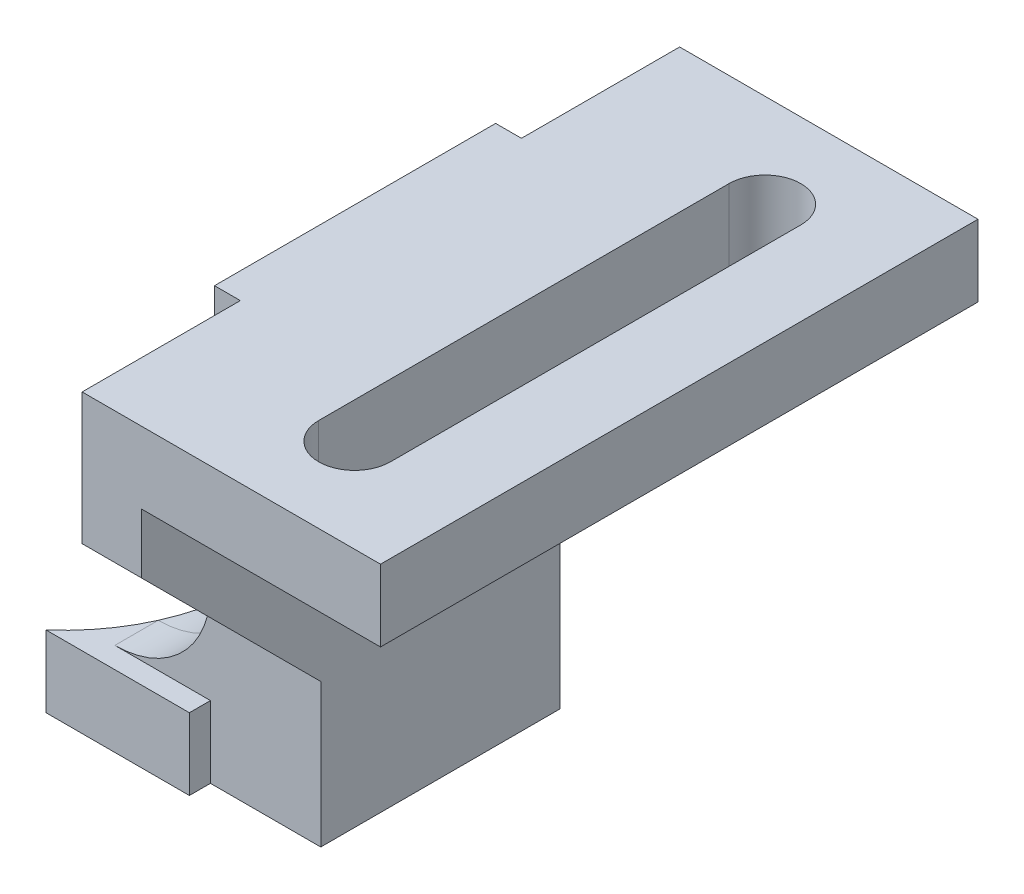
SolidWorks part; units mm, degrees
ref_plane "Front Plane" through (0, 0, 0) normal (0, 0, 1) x (1, 0, 0)
ref_plane "Top Plane" through (0, 0, 0) normal (0, 1, 0) x (1, 0, 0)
ref_plane "Right Plane" through (0, 0, 0) normal (1, 0, 0) x (0, 0, -1)
sketch "Sketch1" plane through (0, 0, 0) normal (0, 1, 0) x (1, 0, 0)
  line L0 (0, 8.5) -> (0, -8.5) construction
  line L1 (-3, -11.3279) -> (3, -11.3279)
  line L2 (-3, -11.3279) -> (-3, 11.3279)
  line L3 (-3, 11.3279) -> (3, 11.3279)
  line L4 (3, -11.3279) -> (3, -5)
  line L5 (-3, -11.3279) -> (3, 11.3279) construction
  line L6 (-3, 11.3279) -> (3, -11.3279) construction
  line L7 (3, -5) -> (7.6154, -5)
  line L8 (7.6154, -5) -> (7.6154, 5)
  line L9 (7.6154, 5) -> (3, 5)
  line L10 (3, 5) -> (3, 11.3279)
  circle A0 centre (0, 8.5) radius 1.5
  circle A1 centre (0, -8.5) radius 1.5
  point P0 (0, 0)
  point P10 (0, 0)
  point P13 (7.6154, 0)
  point P16 (-3, 0)
  dimension "D1" = 3
  dimension "D2" = 17
  dimension "D3" = 6
  dimension "D4" = 10
extrude "Boss-Extrude1" add sketch "Sketch1" along normal blind 3
sketch "Sketch3" plane through (0, 3, 0) normal (0, 1, 0) x (1, 0, 0)
  line L0 (7.6154, 5) -> (3, 5) construction
  line L1 (7.6154, 5) -> (3, 5)
  line L2 (7.6154, 5) -> (7.6154, -5)
  line L3 (7.6154, -5) -> (3, -5)
  line L4 (3, 5) -> (3, -5)
  line L5 (7.6154, -5) -> (7.6154, 5) construction
  line L6 (3, -5) -> (7.6154, -5) construction
extrude "Boss-Extrude2" add sketch "Sketch3" along normal blind 12.9998
fillet "Fillet7" radius 1 2 edges at (3, 1.5, -11.3279) (3, 1.5, 11.3279)
sketch "Sketch7" plane through (0, 0, 0) normal (0, -1, 0) x (1, 0, 0)
  line L0 (-3.6553, -6.3921) -> (-3.7819, 6.4785)
  arc A0 (-3.6553, -6.3921) -> (-3.7819, 6.4785) centre (-8.1114, 0) ccw
extrude "Cut-Extrude4" cut sketch "Sketch7" against normal blind 10
sketch "Sketch9" plane through (0, 15.9998, 0) normal (0, 1, 0) x (1, 0, 0)
  line L1 (4.0509, -12.5) -> (17.6154, -12.5)
  line L2 (4.0509, -12.5) -> (4.0509, 12.5)
  line L3 (4.0509, 12.5) -> (17.6154, 12.5)
  line L4 (17.6154, -12.5) -> (17.6154, 12.5)
  line L6 (7.6154, -5) -> (7.6154, 5) construction
  line L7 (7.6154, -5) -> (17.6154, -5) construction
  line L8 (12.6154, -6) -> (12.6154, 6) construction
  circle A0 centre (12.6154, 6) radius 1.5
  circle A1 centre (12.6154, -6) radius 1.5
  point P7 (7.6154, 0)
  point P8 (4.0509, 0)
  point P16 (12.6154, -5)
  point P18 (12.6154, 0)
  dimension "D3" = 3
  dimension "D1" = 25
  dimension "D2" = 10
  dimension "D4" = 12
extrude "Boss-Extrude3" add sketch "Sketch9" along normal blind 3
chamfer "Chamfer1" distance 10 angle 45 1 edges at (5.8332, 15.9998, 5)
chamfer "Chamfer2" distance 10 angle 45 1 edges at (5.8332, 15.9998, -5)
fillet "Fillet8" radius 4 1 edges at (3, 3, 0)
sketch "Sketch10" plane through (0, 3, 0) normal (0, 1, 0) x (1, 0, 0)
  line L1 (-3, 5.8812) -> (5.1312, 5.8812)
  line L2 (-3, 5.8812) -> (-3, 12.6309)
  line L3 (-3, 12.6309) -> (5.1312, 12.6309)
  line L4 (5.1312, 5.8812) -> (5.1312, 12.6309)
  line L5 (-3, -5.8812) -> (5.1312, -5.8812)
  line L6 (-3, -5.8812) -> (-3, -12.8947)
  line L7 (-3, -12.8947) -> (5.1312, -12.8947)
  line L8 (5.1312, -5.8812) -> (5.1312, -12.8947)
extrude "Cut-Extrude5" cut sketch "Sketch10" against normal through all both and the other way through all
sketch "Sketch11" plane through (0, 18.9998, 0) normal (0, 1, 0) x (1, 0, 0)
  line L0 (14.1154, 8.5849) -> (14.1154, -8.5849)
  line L1 (17.6154, -12.5) -> (17.6154, 12.5) construction
  line L2 (11.1154, 8.5849) -> (11.1154, -8.5849)
  arc A0 (14.1154, -8.5849) -> (11.1154, -8.5849) centre (12.6154, -8.5849) cw
  arc A1 (11.1154, 8.5849) -> (14.1154, 8.5849) centre (12.6154, 8.5849) cw
  point P4 (17.6154, 0)
  point P5 (14.1154, 0)
  dimension "D1" = 3.5
  dimension "D2" = 17.1698
  dimension "D3" = 3
extrude "Cut-Extrude6" cut sketch "Sketch11" against normal blind 10
